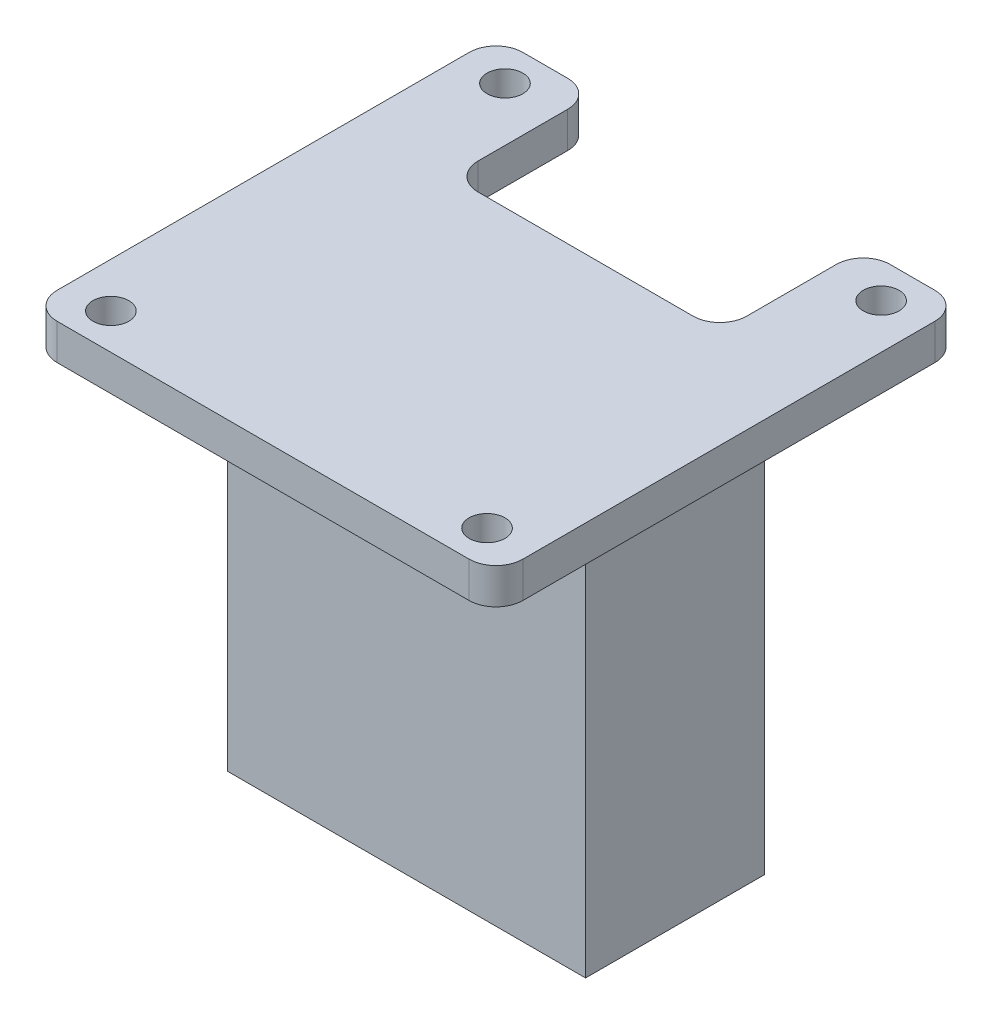
SolidWorks part; units mm, degrees
ref_plane "前视基准面" through (0, 0, 0) normal (0, 0, 1) x (1, 0, 0)
ref_plane "上视基准面" through (0, 0, 0) normal (0, 1, 0) x (1, 0, 0)
ref_plane "右视基准面" through (0, 0, 0) normal (1, 0, 0) x (0, 0, -1)
sketch "草图1" plane through (0, 0, 0) normal (0, 1, 0) x (1, 0, 0)
  line L1 (10, -5) -> (-10, -5)
  line L2 (10, -5) -> (10, 5)
  line L3 (10, 5) -> (-10, 5)
  line L4 (-10, -5) -> (-10, 5)
  circle A0 centre (0, 1.5) radius 1.45
  point P1 (0, 0)
  point P5 (0, 0)
  dimension "D4" = 2.9
  dimension "D1" = 20
  dimension "D2" = 10
extrude "凸台-拉伸1" add sketch "草图1" along normal blind 23
sketch "草图2" plane through (0, 23, 0) normal (0, 1, 0) x (1, 0, 0)
  line L0 (-1000, 0) -> (49000, 0) construction
  line L1 (13, -13) -> (0, -13)
  line L2 (13, -13) -> (13, 13)
  line L3 (13, 13) -> (-13, 13)
  line L4 (-13, -13) -> (-13, 13)
  line L6 (13, 13) -> (-13, -13) construction
  line L7 (0, -1000) -> (0, 49000) construction
  line L12 (0, -13) -> (-13, -13)
  circle A0 centre (-10.5, 11) radius 1
  circle A1 centre (10.5, 11) radius 1
  circle A2 centre (10.5, -11) radius 1
  circle A3 centre (-10.5, -11) radius 1
  point P0 (0, 0)
  point P18 (0, -13)
  point P19 (-0.2258, -13)
  dimension "D2" = 2
  dimension "D3" = 10.5
  dimension "D1" = 26
  dimension "D4" = 11
extrude "凸台-拉伸2" add sketch "草图2" along normal blind 2
sketch "草图3" plane through (0, 25, 0) normal (0, 1, 0) x (1, 0, 0)
  line L0 (13, 13) -> (-13, 13) construction
  line L1 (7.5, 21) -> (-7.5, 21)
  line L2 (7.5, 21) -> (7.5, 5)
  line L3 (7.5, 5) -> (-7.5, 5)
  line L4 (-7.5, 21) -> (-7.5, 5)
  line L5 (7.5, 21) -> (-7.5, 5) construction
  line L6 (7.5, 5) -> (-7.5, 21) construction
  point P0 (0, 13)
  dimension "D1" = 15
  dimension "D2" = 16
extrude "切除-拉伸1" cut sketch "草图3" against normal blind 15
fillet "圆角3" radius 1.5 13 edges at (-13, 24, -13) (-7.5, 24, -13) (13, 24, -13) (7.5, 24, -13) (-13, 24, 13) (13, 24, 13) (-7.5, 24, -5) (7.5, 24, -5) (-8.75, 23, -5) (8.75, 23, -5) (10, 23, 0) (0, 23, 5) (-10, 23, 0)
